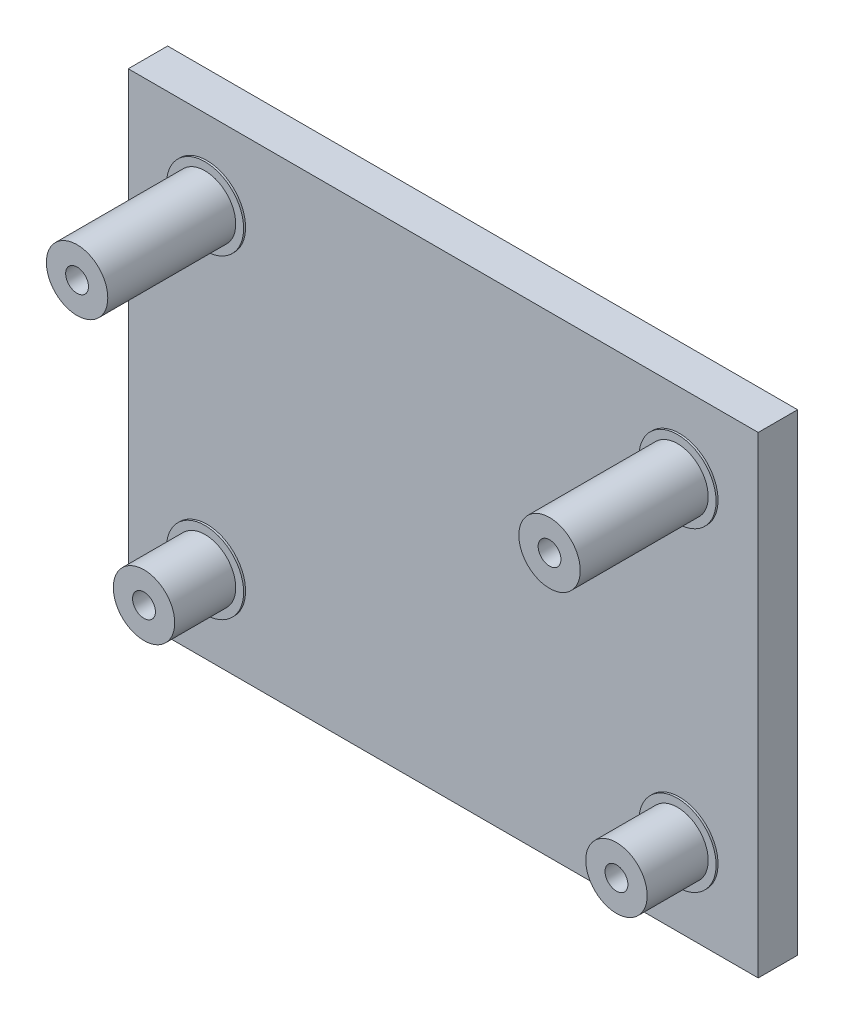
SolidWorks part; units mm, degrees
ref_plane "Front Plane" through (0, 0, 0) normal (0, 0, 1) x (1, 0, 0)
ref_plane "Top Plane" through (0, 0, 0) normal (0, 1, 0) x (1, 0, 0)
ref_plane "Right Plane" through (0, 0, 0) normal (1, 0, 0) x (0, 0, -1)
ref_axis "X" through (-88.99, 0, 0) along (1, 0, 0)
ref_axis "Y" through (0, 55, 0) along (0, -1, 0)
ref_axis "Z" through (0, 0, -88.99) along (0, 0, 1)
sketch "Sketch1" plane through (0, 0, 0) normal (0, 0, 1) x (1, 0, 0)
  line L1 (-30, 20) -> (30, 20) construction
  line L2 (-30, 20) -> (-30, -20) construction
  line L3 (-30, -20) -> (30, -20) construction
  line L4 (30, 20) -> (30, -20) construction
  line L5 (-30, 20) -> (30, -20) construction
  line L6 (-30, -20) -> (30, 20) construction
  line L7 (-40, 30) -> (40, 30)
  line L8 (-40, 30) -> (-40, -30)
  line L9 (-40, -30) -> (40, -30)
  line L10 (40, 30) -> (40, -30)
  line L11 (-40, 30) -> (40, -30) construction
  line L12 (-40, -30) -> (40, 30) construction
  circle A0 centre (-30, 20) radius 3.9
  circle A1 centre (-30, -20) radius 3.9
  circle A2 centre (30, -20) radius 3.9
  circle A3 centre (30, 20) radius 3.9
  circle A4 centre (-30, 20) radius 4.9
  circle A5 centre (30, 20) radius 4.9
  circle A6 centre (30, -20) radius 4.9
  circle A7 centre (-30, -20) radius 4.9
  circle A8 centre (-30, 20) radius 1.45
  circle A9 centre (-30, -20) radius 1.45
  circle A10 centre (30, 20) radius 1.45
  circle A11 centre (30, -20) radius 1.45
  point P0 (0, 0)
  point P10 (0, 0)
  dimension "D1" = 40
  dimension "D3" = 7.8
  dimension "D6" = 1
  dimension "D7" = 2.9
  dimension "D2" = 60
  dimension "D4" = 10
  dimension "D5" = 10
extrude "Boss-Extrude1" add sketch "Sketch1" against normal blind 5 contours L8 L9 L10 L7
extrude "Boss-Extrude2" add sketch "Sketch1<3>" along normal blind 8 contours A1 A9 | A2 A11 region at (-33.7897, -20, 0) region at (26.2103, -20, 0)
sketch "Sketch1<3>" plane through (0, 0, 0) normal (0, 0, 1) x (1, 0, 0) same geometry as "Sketch1"
extrude "Boss-Extrude4" add sketch "Sketch1<5>" along normal blind 16.5 contours A0 A8 | A3 A10 region at (-33.7897, 20, 0) region at (26.2103, 20, 0)
sketch "Sketch1<5>" plane through (0, 0, 0) normal (0, 0, 1) x (1, 0, 0) same geometry as "Sketch1"
extrude "Boss-Extrude3" add sketch "Sketch1<4>" along normal blind 0.25 contours A4 A0 | A5 A3 | A6 A2 | A7 A1 region at (-34.7614, 20, 0) region at (25.2386, 20, 0) region at (25.2386, -20, 0) region at (-34.7614, -20, 0)
sketch "Sketch1<4>" plane through (0, 0, 0) normal (0, 0, 1) x (1, 0, 0) same geometry as "Sketch1"
